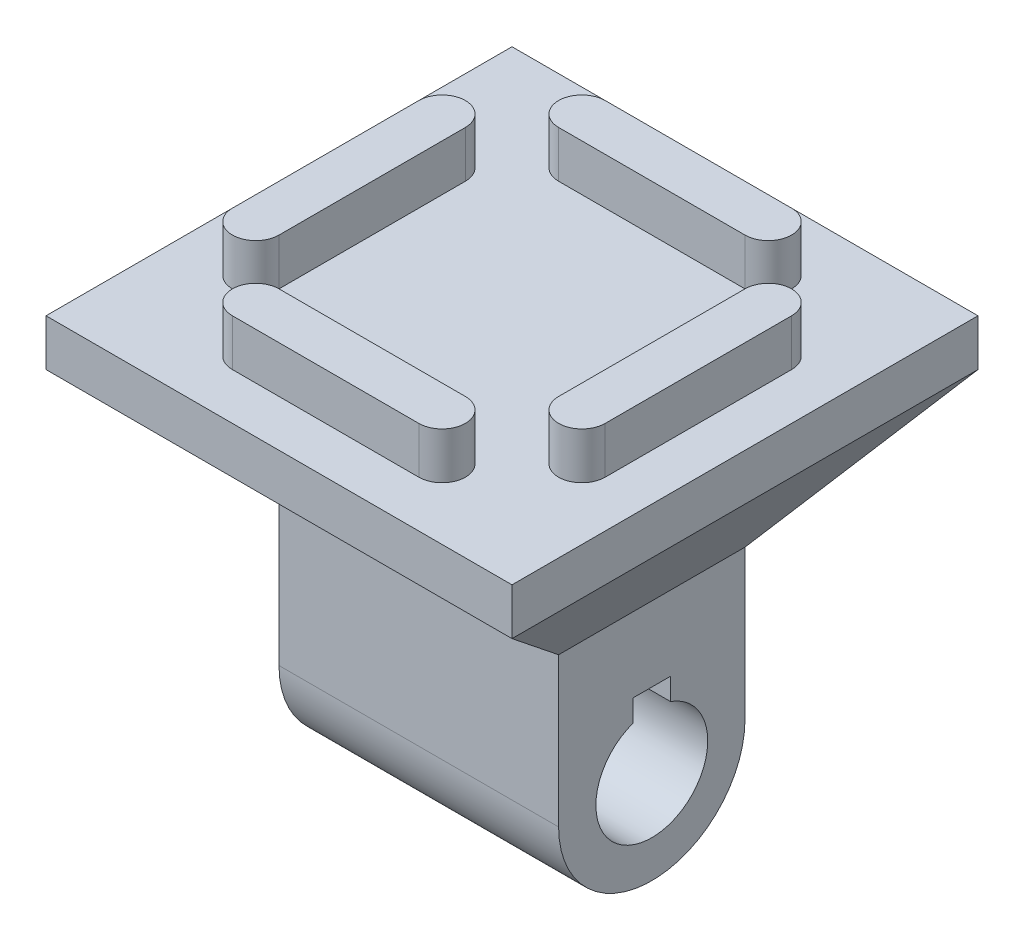
SolidWorks part; units mm, degrees
ref_plane "Front Plane" through (0, 0, 0) normal (0, 0, 1) x (1, 0, 0)
ref_plane "Top Plane" through (0, 0, 0) normal (0, 1, 0) x (1, 0, 0)
ref_plane "Right Plane" through (0, 0, 0) normal (1, 0, 0) x (0, 0, -1)
sketch "Sketch1" plane through (0, 0, 0) normal (0, 1, 0) x (1, 0, 0)
  line L1 (-25, -25) -> (25, -25)
  line L2 (-25, -25) -> (-25, 25)
  line L3 (-25, 25) -> (25, 25)
  line L4 (25, -25) -> (25, 25)
  line L5 (-25, -25) -> (25, 25) construction
  line L6 (-25, 25) -> (25, -25) construction
  point P0 (0, 0)
  dimension "D1" = 50
extrude "Boss-Extrude1" add sketch "Sketch1" along normal blind 5
sketch "Sketch2" plane through (0, 5, 0) normal (0, 1, 0) x (1, 0, 0)
  line L0 (-17.5, 10) -> (-17.5, -10) construction
  line L1 (-44.2539, 0) -> (44.2539, 0) construction
  line L2 (-15, 10) -> (-15, -10)
  line L3 (-20, 10) -> (-20, -10)
  arc A0 (-15, 10) -> (-20, 10) centre (-17.5, 10) ccw
  arc A1 (-20, -10) -> (-15, -10) centre (-17.5, -10) ccw
  point P4 (-17.5, 0)
  dimension "D2" = 15
  dimension "D1" = 20
extrude "Boss-Extrude2" add sketch "Sketch2" along normal blind 5
ref_axis "Axis1" through (0, -43.5149, 0) along (0, 1, 0)
pattern_circular "CirPattern1" count 4 over 360 about axis through (0, -43.5149, 0) along (0, 1, 0) of "Boss-Extrude2"
sketch "Sketch3" plane through (0, 0, 0) normal (1, 0, 0) x (0, 0, -1)
  line L0 (0, 44.2539) -> (0, -44.2539) construction
  line L1 (55, 0) -> (-55, 0) construction
  circle A0 centre (0, -30) radius 6
  circle A1 centre (0, -30) radius 10
  dimension "D1" = 12
  dimension "D2" = 20
  dimension "D3" = 30
extrude "Boss-Extrude3" add sketch "Sketch3" along normal mid plane 30 separate body
ref_plane "Plane1" through (0, -14, 0) normal (0, -1, 0) x (-1, 0, 0)
sketch "Sketch4" plane through (0, -14, 0) normal (0, -1, 0) x (-1, 0, 0)
  line L0 (15, 10) -> (-15, 10) construction
  line L1 (-15, -10) -> (15, -10)
  line L2 (-15, -10) -> (-15, 10)
  line L3 (-15, 10) -> (15, 10)
  line L4 (15, -10) -> (15, 10)
  line L5 (-15, -10) -> (15, 10) construction
  line L6 (-15, 10) -> (15, -10) construction
  point P0 (0, 0)
extrude "Boss-Extrude4" add sketch "Sketch4" along normal up to next
loft "Loft1" add section face at (0, -14, 0) section face at (0, 0, 0) connector at (-15, -14, 10) connector at (-25, 0, 25)
sketch "Sketch5" plane through (-15, 0, 0) normal (-1, 0, 0) x (0, 0, 1)
  line L0 (0, -44.2539) -> (0, 44.2539) construction
  line L1 (-2, -26) -> (2, -26)
  line L2 (-2, -26) -> (-2, -22)
  line L3 (-2, -22) -> (2, -22)
  line L4 (2, -26) -> (2, -22)
  line L5 (-2, -26) -> (2, -22) construction
  line L6 (-2, -22) -> (2, -26) construction
  circle A1 centre (0, -30) radius 6 construction
  point P0 (0, -24)
  dimension "D1" = 4
  dimension "D2" = 4
  dimension "D3" = 6
extrude "Cut-Extrude2" cut sketch "Sketch5" against normal blind 30
